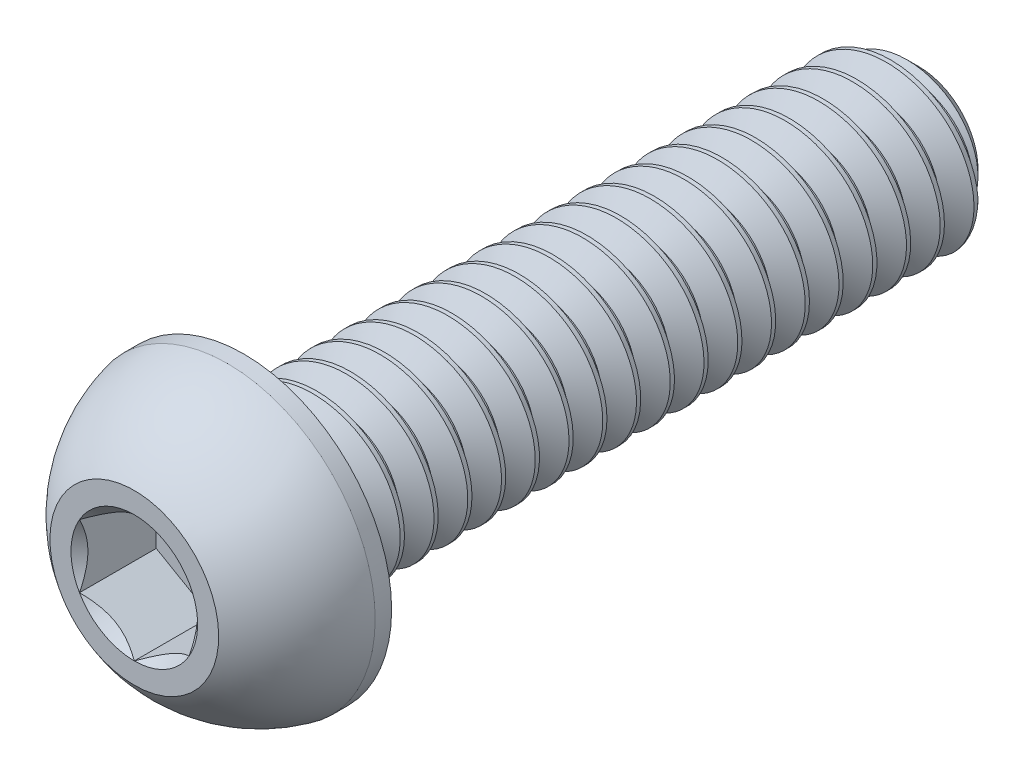
SolidWorks part; units mm, degrees
ref_plane "Front" through (0, 0, 0) normal (0, 0, 1) x (1, 0, 0)
ref_plane "Top" through (0, 0, 0) normal (0, 1, 0) x (1, 0, 0)
ref_plane "Right" through (0, 0, 0) normal (1, 0, 0) x (0, 0, -1)
sketch "Sketch1" plane through (0, 0, 0) normal (1, 0, 0) x (0, 0, -1)
  line L2 (1.3, 1) -> (9.3, 1)
  line L3 (9.3, 1) -> (9.3, 0)
  line L4 (9.3, 0) -> (1.3, 0)
  line L6 (1.105, 1.75) -> (1.3, 1.75) construction
  line L7 (9.3, 1) -> (9.3, -1) construction
  line L8 (0, 0) -> (1.3, 0) construction
  line L9 (1.3, 1.75) -> (1.3, -1.75) construction
  line L11 (1.3, 1) -> (1.3, 0)
  line L13 (0, 0.65) -> (0, -0.65) construction
  line L14 (0, 0.65) -> (0, 1) construction
  arc A3 (0, 1) -> (1.105, 1.75) centre (1.4858, 0) cw construction
  dimension "D1" = 0.195
revolve "Revolve1" add sketch "Sketch1" angle 360 mid plane about L4
sketch "Sketch3" plane through (0, 0, -9.3) normal (0, 0, -1) x (-1, 0, 0)
  circle A0 centre (0, 0) radius 1
curve "Helix/Spiral1" pitch 0.4 height 8.4 radius 1 centre (0, 0, -9.3) axis (0, 0, 1) start towards (0, 1, 0)
sketch "Sketch2" plane through (0, 0, 0) normal (1, 0, 0) x (0, 0, -1)
  line L0 (9.3, 1) -> (9.65, 1)
  line L1 (9.65, 1) -> (9.5, 0.7402)
  line L2 (9.5, 0.7402) -> (9.45, 0.7402)
  line L3 (9.45, 0.7402) -> (9.3, 1)
  line L4 (9.375, 0.8701) -> (9.575, 0.8701) construction
  dimension "D1" = 60
  dimension "D2" = 0.05
  dimension "D3" = 0.2
chamfer "Chamfer1" distance 0.3 angle 45 1 edges at (0, 1, -9.3)
sweep "Cut-Sweep1" cut profiles "Sketch2" path "Helix/Spiral1" align with end faces yes
sketch "Sketch7" plane through (0, 0, 0) normal (1, 0, 0) x (0, 0, -1)
  line L6 (1.105, 1.75) -> (1.3, 1.75) construction
  line L8 (0, 0) -> (1.3, 0) construction
  line L11 (1.3, 1.75) -> (1.3, -1.75) construction
  line L12 (1.105, 1.75) -> (1.3, 1.75)
  line L13 (0, 0) -> (1.3, 0)
  line L14 (0, 0.65) -> (0, -0.65) construction
  line L15 (1.3, 1.75) -> (1.3, 0)
  line L16 (0, 1) -> (0, 0)
  arc A2 (1.105, 1.75) -> (0, 1) centre (1.4858, 0) ccw construction
  arc A3 (1.105, 1.75) -> (0, 1) centre (1.4858, 0) ccw
revolve "Revolve2" add sketch "Sketch7" angle 360 mid plane about L13
sketch "Sketch5" plane through (0, 0, 0) normal (0, 0, 1) x (1, 0, 0)
  line L1 (0.65, -0.3753) -> (0.65, 0.3753)
  line L2 (0.65, 0.3753) -> (0, 0.7506)
  line L3 (0, 0.7506) -> (-0.65, 0.3753)
  line L4 (-0.65, 0.3753) -> (-0.65, -0.3753)
  line L5 (-0.65, -0.3753) -> (0, -0.7506)
  line L6 (0, -0.7506) -> (0.65, -0.3753)
  circle A0 centre (0, 0) radius 0.65 construction
extrude "Cut-Extrude2" cut sketch "Sketch5" against normal blind 0.91
sketch "Sketch6" plane through (0, 0, 0) normal (0, 0, 1) x (1, 0, 0)
  circle A0 centre (0, 0) radius 0.7506
extrude "Cut-Extrude3" cut sketch "Sketch6" against normal blind 0.91 draft 45
sketch "Sketch9" [suppressed] plane through (0, 0, -4.2164) normal (0, 0, 1) x (1, 0, 0)
  circle A2 centre (0, 0) radius 3.9687
extrude "Boss-Extrude2" [suppressed] add sketch "Sketch9" against normal offset from surface (9.525 mm away) 28.575 up to face at (0, 0.7, -9.3)
sketch "Sketch10" plane through (0, 0, 0) normal (1, 0, 0) x (0, 0, -1)
  line L0 (9.3, 1) -> (9.3, -1) construction
  point P0 (8.7, -1)
  dimension "D1" = 0.6
equation "\"D3@Helix/Spiral1\" = \"Lg@Sketch1\" + \"D4@Helix/Spiral1\""
equation "\"D2@Sketch2\" = \"D4@Helix/Spiral1\" * .125"
equation "\"D3@Sketch2\" = \"D4@Helix/Spiral1\" * .5"
equation "\"D1@Chamfer1\" = \"D4@Helix/Spiral1\" * .75"
equation "\"D1@Cut-Extrude2\" = \"Head Ht@Sketch1\" * .7"
equation "\"D1@Sketch1\" = \"Head Ht@Sketch1\" * .15"
equation "\"D1@Sketch10\" = \"D4@Helix/Spiral1\" * 1.5"
equation "\"D1@Cut-Extrude3\" = \"D1@Cut-Extrude2\""
